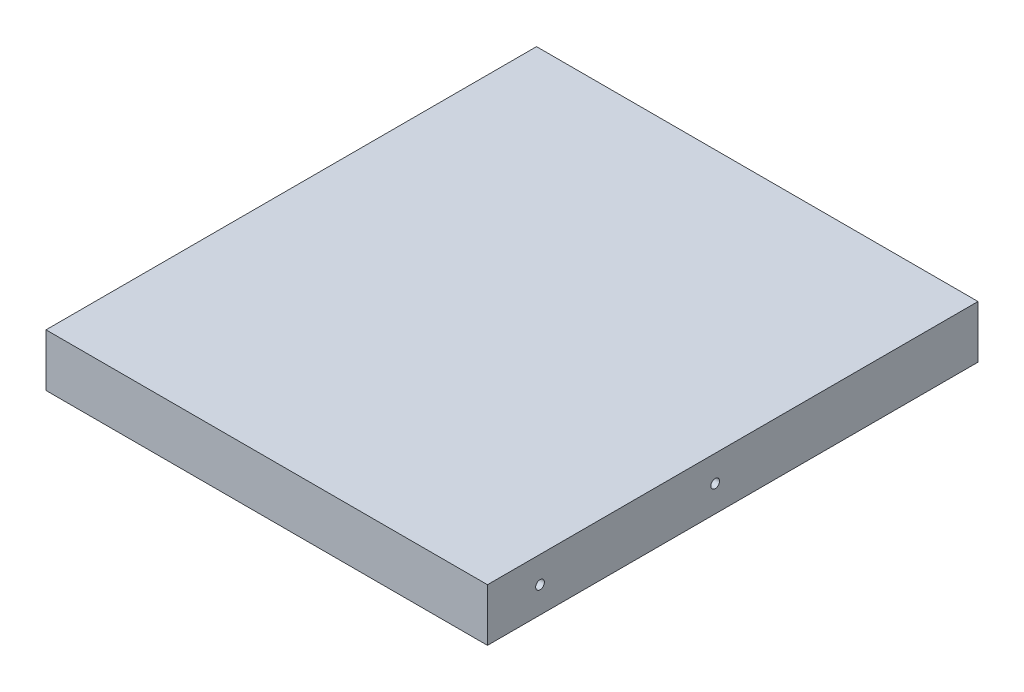
SolidWorks part; units mm, degrees
material "Beech"
ref_plane "Front Plane" through (0, 0, 0) normal (0, 0, 1) x (1, 0, 0)
ref_plane "Top Plane" through (0, 0, 0) normal (0, 1, 0) x (1, 0, 0)
ref_plane "Right Plane" through (0, 0, 0) normal (1, 0, 0) x (0, 0, -1)
sketch "Sketch1" plane through (0, 0, 0) normal (0, 0, 1) x (1, 0, 0)
  line L0 (80.01, 5194.3) -> (80.01, 5935.98) construction
  line L1 (-80.01, 5846.1044) -> (80.01, 5846.1044)
  line L2 (-80.01, 5846.1044) -> (-80.01, 5827.0544)
  line L3 (-80.01, 5827.0544) -> (80.01, 5827.0544)
  line L4 (80.01, 5846.1044) -> (80.01, 5827.0544)
  line L5 (-80.01, 5194.3) -> (-80.01, 5935.98) construction
  line L6 (-80.01, 5827.0544) -> (-99.06, 5827.0544) construction
  dimension "D1" = 19.05
extrude "Boss-Extrude1" add sketch "Sketch1" along normal offset from surface (177.8 mm away) 101.6 offset beyond the face yes
hole_wizard "Hole1" positions "Sketch2" profile "Sketch3" legacy
sketch "Sketch2" plane through (0, 0, -19.05) normal (0, 0, -1) x (-1, 0, 0)
  line L1 (0, 5194.3) -> (0, 5935.98) construction
  line L9 (80.01, 5836.5794) -> (-80.01, 5836.5794) construction
  point P1 (0.1622, 5756.275)
  point P4 (0, 5926.455)
  point P16 (-203.2, 5926.455)
  point P28 (-406.4, 5926.455)
  point P31 (-406.5622, 5756.275)
  point P43 (-203.3622, 5756.275)
  point P55 (-359.618, 5737.225)
  point P61 (-428.6139, 5737.225)
  point P64 (-421.2578, 5578.475)
  point P70 (-319.6578, 5578.475)
  point P82 (-116.4578, 5578.475)
  point P85 (-424.0726, 5559.425)
  point P91 (-358.1042, 5559.425)
  point P94 (-418.2303, 5400.675)
  point P100 (-316.6303, 5400.675)
  point P112 (-113.4303, 5400.675)
  point P115 (-419.5313, 5381.625)
  point P121 (-356.5904, 5381.625)
  point P124 (-415.2028, 5222.875)
  point P130 (-313.6028, 5222.875)
  point P144 (-110.4028, 5222.875)
  point P147 (-414.9901, 5203.825)
  point P153 (-355.0767, 5203.825)
  point P159 (355.0767, 5203.825)
  point P161 (414.9901, 5203.825)
  point P162 (110.4028, 5222.875)
  point P166 (313.6028, 5222.875)
  point P168 (415.2028, 5222.875)
  point P169 (356.5904, 5381.625)
  point P171 (419.5313, 5381.625)
  point P172 (113.4303, 5400.675)
  point P176 (316.6303, 5400.675)
  point P178 (418.2303, 5400.675)
  point P179 (358.1042, 5559.425)
  point P181 (424.0726, 5559.425)
  point P182 (116.4578, 5578.475)
  point P186 (319.6578, 5578.475)
  point P188 (421.2578, 5578.475)
  point P189 (428.6139, 5737.225)
  point P191 (359.618, 5737.225)
  point P195 (203.3622, 5756.275)
  point P199 (406.5622, 5756.275)
  point P200 (406.4, 5926.455)
  point P204 (203.2, 5926.455)
  point P208 (-0.1622, 5756.275)
  point P252 (0, 5836.5794)
  point P254 (-60.96, 5836.5794)
  point P256 (60.96, 5836.5794)
  point P257 (0, 0)
  point P258 (0, 0)
  point P259 (0, 0)
  point P260 (0, 0)
  point P261 (0, 0)
  point P262 (0, 0)
  point P263 (0, 0)
  point P264 (0, 0)
  point P265 (0, 0)
sketch "Sketch3" plane through (-0.1622, 5756.275, -19.05) normal (1, 0, 0) x (0, 1, 0)
  line L0 (0, 0) -> (0, 32.346)
  line L1 (0, 32.346) -> (0.9919, 31.75)
  line L2 (0.9919, 31.75) -> (0.9919, 4.7029)
  line L3 (0.9919, 4.7029) -> (5.08, 0)
  line L4 (5.08, 0) -> (0, 0)
  line L5 (0, -14.3089) -> (0, 102.4216) construction
  line L6 (0, 32.346) -> (-0.9919, 31.75) construction
  line L7 (-0.9919, 4.7029) -> (-5.08, 0) construction
  dimension "Diameter" = 1.9837
  dimension "Depth" = 31.75
  dimension "C-Sink Diameter" = 10.16
  dimension "C-Sink Angle" = 82
  dimension "Drill Angle" = 118
hole_wizard "Hole3" positions "Sketch6" profile "Sketch7" legacy
sketch "Sketch6" plane through (99.06, 0, -2683.51) normal (1, 0, 0) x (0, 0, -1)
  line L0 (-2759.71, 5836.5794) -> (-2861.31, 5836.5794) construction
  point P13 (-2842.26, 5836.5794)
  point P15 (-2778.76, 5836.5794)
sketch "Sketch7" plane through (99.06, 5836.5794, 95.25) normal (0, 1, 0) x (0, 0, -1)
  line L0 (0, 0) -> (0, 32.7039)
  line L1 (0, 32.7039) -> (1.5875, 31.75)
  line L2 (1.5875, 31.75) -> (1.5875, 4.0177)
  line L3 (1.5875, 4.0177) -> (5.08, 0)
  line L4 (5.08, 0) -> (0, 0)
  line L5 (0, -14.3089) -> (0, 102.4216) construction
  line L6 (0, 32.7039) -> (-1.5875, 31.75) construction
  line L7 (-1.5875, 4.0177) -> (-5.08, 0) construction
  dimension "Diameter" = 3.175
  dimension "Depth" = 31.75
  dimension "C-Sink Diameter" = 10.16
  dimension "C-Sink Angle" = 82
  dimension "Drill Angle" = 118
hole_wizard "Hole4" positions "Sketch8" profile "Sketch9" legacy
sketch "Sketch8" plane through (-99.06, 0, -2683.51) normal (-1, 0, 0) x (0, 0, 1)
  line L0 (2759.71, 5836.5794) -> (2861.31, 5836.5794) construction
  point P12 (2842.26, 5836.5794)
  point P14 (2778.76, 5836.5794)
sketch "Sketch9" plane through (-99.06, 5836.5794, 95.25) normal (0, 1, 0) x (0, 0, 1)
  line L0 (0, 0) -> (0, 32.7039)
  line L1 (0, 32.7039) -> (1.5875, 31.75)
  line L2 (1.5875, 31.75) -> (1.5875, 4.0177)
  line L3 (1.5875, 4.0177) -> (5.08, 0)
  line L4 (5.08, 0) -> (0, 0)
  line L5 (0, -14.3089) -> (0, 102.4216) construction
  line L6 (0, 32.7039) -> (-1.5875, 31.75) construction
  line L7 (-1.5875, 4.0177) -> (-5.08, 0) construction
  dimension "Diameter" = 3.175
  dimension "Depth" = 31.75
  dimension "C-Sink Diameter" = 10.16
  dimension "C-Sink Angle" = 82
  dimension "Drill Angle" = 118
